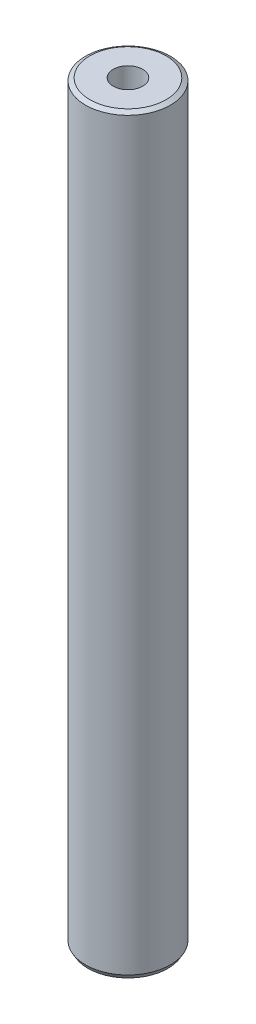
SolidWorks part; units mm, degrees
ref_plane "Front Plane" through (0, 0, 0) normal (0, 0, 1) x (1, 0, 0)
ref_plane "Top Plane" through (0, 0, 0) normal (0, 1, 0) x (1, 0, 0)
ref_plane "Right Plane" through (0, 0, 0) normal (1, 0, 0) x (0, 0, -1)
sketch "Sketch1" plane through (0, 0, 0) normal (0, 1, 0) x (1, 0, 0)
  circle A0 centre (0, 0) radius 20
  dimension "SHAFT_OD" = 40
extrude "Boss-Extrude1" add sketch "Sketch1" along normal blind 353.9473
sketch "Sketch2" plane through (0, 0, 0) normal (0, 1, 0) x (1, 0, 0)
  circle A0 centre (0, 0) radius 6.93
  dimension "BORE_D" = 13.86
extrude "Cut-Extrude1" cut sketch "Sketch2" along normal through all
chamfer "Chamfer1" distance 1.19 angle 60 2 edges at (0, 353.9473, 20) (0, 0, 20) first distance on face at (0, 353.9473, 20) first distance on face at (0, 0, 6.93)
